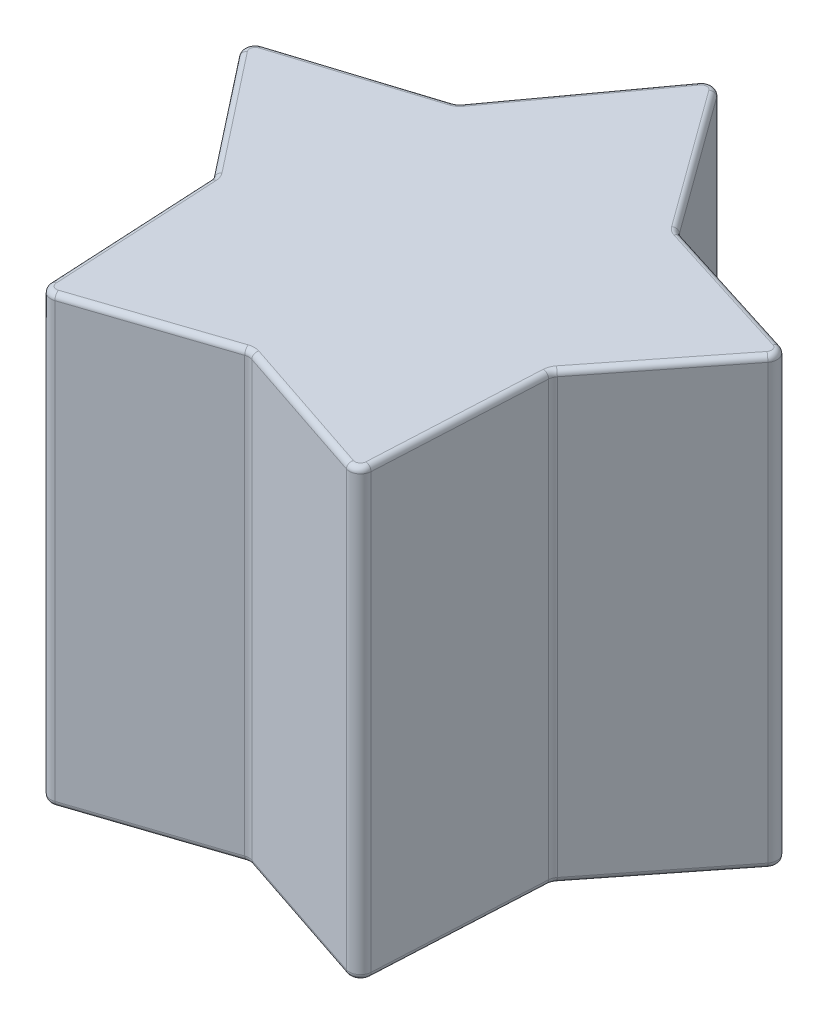
SolidWorks part; units mm, degrees
ref_plane "Front Plane" through (0, 0, 0) normal (0, 0, 1) x (1, 0, 0)
ref_plane "Top Plane" through (0, 0, 0) normal (0, 1, 0) x (1, 0, 0)
ref_plane "Right Plane" through (0, 0, 0) normal (1, 0, 0) x (0, 0, -1)
sketch "Sketch2" plane through (0, 0, 0) normal (0, 1, 0) x (1, 0, 0)
  line L0 (2.4572, -35.885) -> (2.4572, 18.1831) construction
  line L1 (-11.9684, -2.2548) -> (-12.7681, 12.9344)
  line L2 (3.2649, 42.4487) -> (12.2156, 30.1442)
  line L3 (15.5646, -3.1497) -> (2.7744, 1.1274)
  line L4 (-20.8205, 25.6799) -> (-7.8205, 29.7966)
  line L5 (26.214, 24.1069) -> (17.8646, 13.5124)
  line L6 (-7.3144, 30.1607) -> (1.6482, 42.4497)
  line L7 (12.7237, 29.7787) -> (25.7292, 25.6796)
  line L8 (2.1401, 1.1274) -> (-10.6527, -3.1506)
  line L9 (-12.98, 13.4991) -> (-21.3053, 24.1092)
  line L10 (17.6513, 12.9441) -> (16.8805, -2.252)
  line L11 (2.4572, 1.2334) -> (2.4572, 43.559) construction
  line L12 (2.4572, 17.809) -> (56.515, 17.809) construction
  line L13 (-22.1959, 25.2443) -> (27.1104, 25.2443) construction
  line L14 (-11.8993, -3.5674) -> (16.8138, -3.5674) construction
  circle A0 centre (2.4572, 17.809) radius 16.5756 construction
  circle A1 centre (2.4572, 17.809) radius 25.75 construction
  arc A2 (-7.3144, 30.1607) -> (-7.8205, 29.7966) centre (-8.1224, 30.7499) cw
  arc A3 (-21.3053, 24.1092) -> (-20.8205, 25.6799) centre (-20.5186, 24.7265) cw
  arc A4 (-12.7681, 12.9344) -> (-12.98, 13.4991) centre (-13.7667, 12.8818) ccw
  arc A5 (-11.9684, -2.2548) -> (-10.6527, -3.1506) centre (-10.9698, -2.2022) ccw
  arc A6 (2.1401, 1.1274) -> (2.7744, 1.1274) centre (2.4572, 0.179) cw
  arc A7 (15.5646, -3.1497) -> (16.8805, -2.252) centre (15.8818, -2.2014) ccw
  arc A8 (17.8646, 13.5124) -> (17.6513, 12.9441) centre (18.6501, 12.8935) ccw
  arc A9 (25.7292, 25.6796) -> (26.214, 24.1069) centre (25.4286, 24.7259) cw
  arc A10 (12.7237, 29.7787) -> (12.2156, 30.1442) centre (13.0243, 30.7325) cw
  arc A11 (3.2649, 42.4487) -> (1.6482, 42.4497) centre (2.4562, 41.8605) ccw
  dimension "D1" = 51.5
  dimension "D2" = 1
  dimension "D3" = 32.4168
  dimension "D4" = 13
extrude "Boss-Extrude2" add sketch "Sketch2" along normal blind 40
fillet "Fillet1" radius 0.5 40 edges at (-14.3205, 0, -27.7382) (-21.4741, 0, -25.0215) (-17.1427, 0, -18.8042) (-12.8305, 0, -13.2331) (-12.3683, 0, -5.3398) (-11.5326, 0, 3.0288) (-4.2563, 0, 1.0116) (2.4572, 0, -1.179) (9.1695, 0, 1.0112) (16.4454, 0, 3.0274) (17.2659, 0, -5.346) (17.7138, 0, -13.2448) (22.0393, 0, -18.8097) (26.3842, 0, -25.0205) (19.2264, 0, -27.7292) (12.4403, 0, -29.9207) (7.7402, 0, -36.2965) (2.4568, 0, -42.8605) (-2.8331, 0, -36.3052) (-7.5383, 0, -29.9382) (-2.8331, 40, -36.3052) (2.4568, 40, -42.8605) (7.7402, 40, -36.2965) (12.4403, 40, -29.9207) (19.2264, 40, -27.7292) (26.3842, 40, -25.0205) (22.0393, 40, -18.8097) (17.7138, 40, -13.2448) (17.2659, 40, -5.346) (16.4454, 40, 3.0274) (9.1695, 40, 1.0112) (2.4572, 40, -1.179) (-4.2563, 40, 1.0116) (-11.5326, 40, 3.0288) (-12.3683, 40, -5.3398) (-12.8305, 40, -13.2331) (-17.1427, 40, -18.8042) (-21.4741, 40, -25.0215) (-14.3205, 40, -27.7382) (-7.5383, 40, -29.9382)
